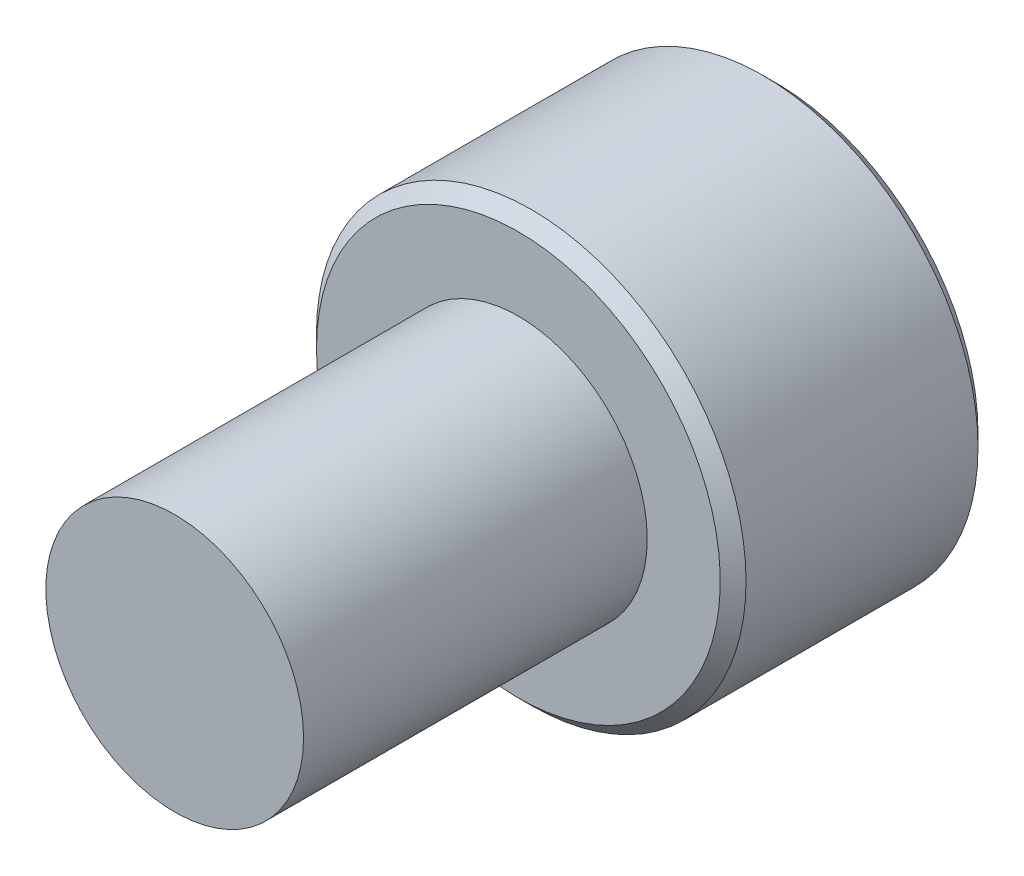
SolidWorks part; units mm, degrees
ref_plane "Front Plane" through (0, 0, 0) normal (0, 0, 1) x (1, 0, 0)
ref_plane "Top Plane" through (0, 0, 0) normal (0, 1, 0) x (1, 0, 0)
ref_plane "Right Plane" through (0, 0, 0) normal (1, 0, 0) x (0, 0, -1)
sketch "Sketch1" plane through (0, 0, 0) normal (0, 0, 1) x (1, 0, 0)
  circle A0 centre (0, 0) radius 3
  dimension "OD" = 6
extrude "Extrude1" add sketch "Sketch1" against normal blind 8
sketch "Sketch2" plane through (0, 0, 0) normal (0, 0, 1) x (1, 0, 0)
  circle A0 centre (0, 0) radius 3 construction
  circle A1 centre (0, 0) radius 3
curve "Helix/Spiral1" pitch 1 height 9 turns 9 parameters "pitch"=1
sketch "Sketch3" plane through (0, 0, 0) normal (1, 0, 0) x (0, 0, -1)
  line L0 (-0.875, 3) -> (-0.5, 2.3505)
  line L1 (-0.5, 2.3505) -> (-0.375, 2.3505)
  line L2 (-0.375, 2.3505) -> (0, 3)
  line L3 (-0.875, 3) -> (0, 3)
  line L4 (-0.4375, 3) -> (-0.4375, 2.3505) construction
  line L5 (-0.6875, 2.6752) -> (-0.1875, 2.6752) construction
  line L6 (0, 3) -> (0, -3) construction
  line L7 (0, -3) -> (8, -3) construction
  point P11 (4.5, -3)
  dimension "D1" = 0.125
  dimension "D2" = 0.5
  dimension "D3" = 60
  dimension "D4" = 4.5
sweep "Cut-Sweep1" [suppressed] cut profiles "Sketch3" path "Helix/Spiral1"
sketch "Sketch4" plane through (0, 0, 0) normal (1, 0, 0) x (0, 0, -1)
  line L0 (0.6327, 3) -> (0, 2.0965)
  line L1 (0, 2.0965) -> (0, 3)
  line L2 (0.6327, 3) -> (0, 3)
  line L3 (-0.875, 3) -> (0, 3) construction
  line L4 (0, 0) -> (7.0209, 0) construction
  dimension "D1" = 55
  dimension "D2" = 0.254
revolve "Cut-Revolve1" [suppressed] cut sketch "Sketch4" angle 360 about L4
sketch "Sketch5" [suppressed] plane through (0, 0, 0) normal (1, 0, 0) x (0, 0, -1)
  line L0 (8, -2.3644) -> (8, 2.1406) construction
  line L1 (8, 3) -> (0.1203, 3)
  line L2 (8, 3) -> (8, 0)
  line L3 (8, 0) -> (0.0001, 0)
  line L4 (0.0001, 2.6698) -> (0.0001, 0)
  line L5 (0.1203, 3) -> (0.0001, 2.6698)
  line L6 (0, 0) -> (9.9695, 0) construction
  point P3 (0.0001, 3)
  point P10 (0.0001, 3)
  dimension "D1" = 0.3302
  dimension "Thread min" = 0.0001
  dimension "D3" = 20
revolve "partially thread" [suppressed] add sketch "Sketch5" angle 360 about L6
sketch "Sketch6" plane through (0, 0, -8) normal (0, 0, -1) x (-1, 0, 0)
  circle A0 centre (0, 0) radius 5
  dimension "head dia" = 10
extrude "Extrude2" add sketch "Sketch6" along normal blind 6
sketch "Sketch7" plane through (0, 0, -14) normal (0, 0, -1) x (-1, 0, 0)
  line L1 (0, 2.8868) -> (-2.5, 1.4434)
  line L2 (-2.5, 1.4434) -> (-2.5, -1.4434)
  line L3 (-2.5, -1.4434) -> (0, -2.8868)
  line L4 (0, -2.8868) -> (2.5, -1.4434)
  line L5 (2.5, -1.4434) -> (2.5, 1.4434)
  line L6 (2.5, 1.4434) -> (0, 2.8868)
  circle A0 centre (0, 0) radius 2.5 construction
  dimension "hex dia" = 5
extrude "Cut-Extrude1" cut sketch "Sketch7" against normal blind 3.75
sketch "Sketch8" plane through (0, 0, -14) normal (0, 0, -1) x (-1, 0, 0)
  circle A0 centre (0, 0) radius 2.8868
extrude "Cut-Extrude2" cut sketch "Sketch8" against normal through all draft 45
chamfer "Chamfer1" distance 0.3 angle 45 2 edges at (-5, 0, -14) (-5, 0, -8)
sketch "Sketch9" plane through (0, 0, 0) normal (1, 0, 0) x (0, 0, -1)
  line L0 (0, 3) -> (0, -3) construction
  line L1 (5.5, 3) -> (5.5, -3) construction
  dimension "D1" = 5.5
sketch "Sketch10" plane through (0, 0, 0) normal (1, 0, 0) x (0, 0, -1)
  line L0 (8, 3) -> (8, 0)
  line L1 (8, 3) -> (7.75, 3)
  line L2 (7.75, 3) -> (6.5074, 0)
  line L3 (8, 0) -> (6.5074, 0)
  line L4 (8, 4.7) -> (8, -4.7) construction
  dimension "D1" = 22.5
  dimension "D2" = 0.25
revolve "Revolve1" add sketch "Sketch10" angle 360 about L3
equation "\"D3@Helix/Spiral1\" = \"screw length@Extrude1\"+\"pitch@Helix/Spiral1\""
equation "\"D1@Sketch3\" = \"pitch@Helix/Spiral1\"*.125"
equation "\"D2@Sketch3\" = \"pitch@Helix/Spiral1\"*.5"
equation "\"D1@Cut-Extrude1\" = \"hex dia@Sketch7\"*.75"
equation "\"D1@Chamfer1\" = \"head dia@Sketch6\"*.03"
equation "\"D1@Sketch9\" = \"pitch@Helix/Spiral1\"*5.5"
equation "\"D2@Sketch10\" = \"pitch@Helix/Spiral1\"*.25"
equation "\"D4@Sketch3\" = \"pitch@Helix/Spiral1\"*4.50"
